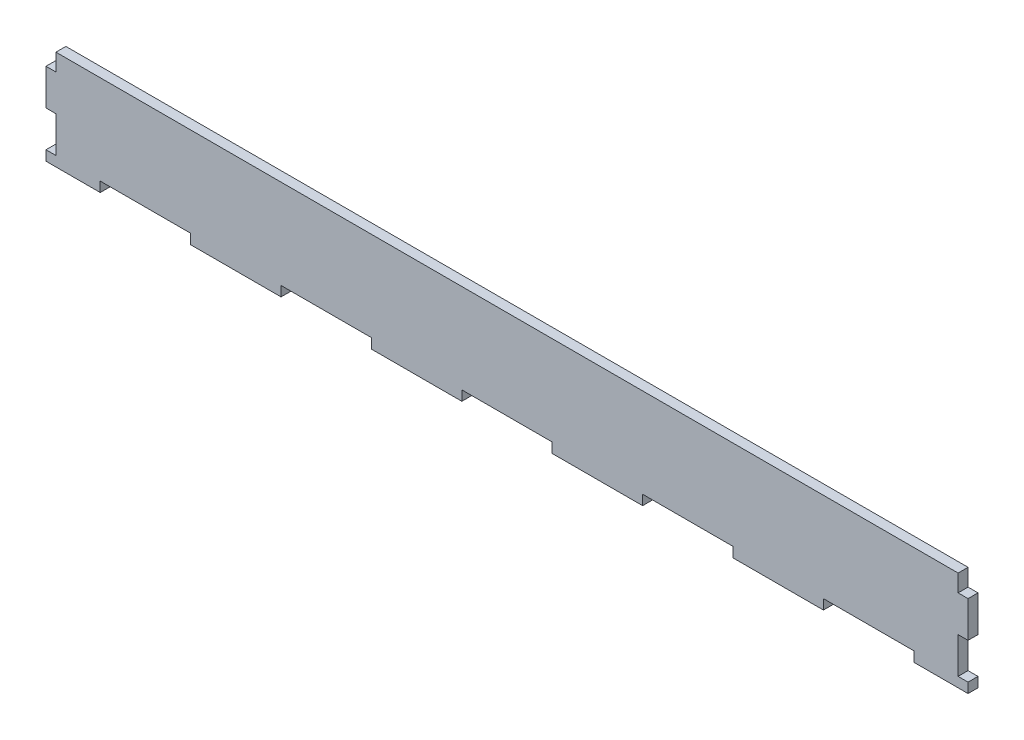
SolidWorks part; units mm, degrees
material "ﾁｰｸ材"
ref_plane "正面" through (0, 0, 0) normal (0, 0, 1) x (1, 0, 0)
ref_plane "平面" through (0, 0, 0) normal (0, 1, 0) x (1, 0, 0)
ref_plane "右側面" through (0, 0, 0) normal (1, 0, 0) x (0, 0, -1)
sketch "ｽｹｯﾁ1" plane through (0, 0, 0) normal (0, 0, 1) x (1, 0, 0)
  line L1 (255, 27.5) -> (-255, 27.5)
  line L2 (255, 27.5) -> (255, -27.5)
  line L3 (255, -27.5) -> (-255, -27.5)
  line L4 (-255, 27.5) -> (-255, -27.5)
  line L5 (255, 27.5) -> (-255, -27.5) construction
  line L6 (255, -27.5) -> (-255, 27.5) construction
  point P0 (0, 0)
  dimension "D1" = 55
  dimension "D2" = 510
extrude "ﾎﾞｽ - 押し出し1" add sketch "ｽｹｯﾁ1" along normal blind 5.5
sketch "ｽｹｯﾁ2" plane through (0, 0, 5.5) normal (0, 0, 1) x (1, 0, 0)
  line L0 (-255, -27.5) -> (255, -27.5) construction
  line L1 (-25, -27.5) -> (25, -27.5)
  line L2 (-25, -27.5) -> (-25, -22)
  line L3 (-25, -22) -> (25, -22)
  line L4 (25, -27.5) -> (25, -22)
  line L5 (-125, -27.5) -> (-75, -27.5)
  line L6 (75, -27.5) -> (125, -27.5)
  line L7 (75, -27.5) -> (75, -22)
  line L8 (75, -22) -> (125, -22)
  line L9 (125, -27.5) -> (125, -22)
  line L10 (-125, -27.5) -> (-125, -22)
  line L11 (-125, -22) -> (-75, -22)
  line L12 (-75, -27.5) -> (-75, -22)
  line L13 (175, -27.5) -> (225, -27.5)
  line L14 (175, -27.5) -> (175, -22)
  line L15 (175, -22) -> (225, -22)
  line L16 (225, -27.5) -> (225, -22)
  line L17 (-225, -27.5) -> (-175, -27.5)
  line L18 (-225, -27.5) -> (-225, -22)
  line L19 (-225, -22) -> (-175, -22)
  line L20 (-175, -27.5) -> (-175, -22)
  point P6 (0, -27.5)
  dimension "D1" = 5.5
  dimension "D2" = 50
  dimension "D3" = 5.5
  dimension "D4" = 50
  dimension "D5" = 50
  dimension "D6" = 50
  dimension "D7" = 5.5
  dimension "D8" = 50
  dimension "D9" = 5.5
  dimension "D10" = 50
  dimension "D11" = 50
  dimension "D12" = 50
  dimension "D13" = 50
extrude "ｶｯﾄ - 押し出し1" cut sketch "ｽｹｯﾁ2" against normal through all
sketch "ｽｹｯﾁ3" plane through (0, 0, 5.5) normal (0, 0, 1) x (1, 0, 0)
  line L0 (255, -27.5) -> (255, 27.5) construction
  line L1 (255, -22) -> (249.5, -22)
  line L2 (255, -22) -> (255, -2)
  line L3 (255, -2) -> (249.5, -2)
  line L4 (249.5, -22) -> (249.5, -2)
  line L5 (225, -27.5) -> (255, -27.5) construction
  line L6 (255, 18) -> (255, 38)
  line L7 (255, 18) -> (249.5, 18)
  line L8 (249.5, 18) -> (249.5, 38)
  line L9 (255, 38) -> (249.5, 38)
  line L10 (0, 0) -> (0, 15.2568) construction
  line L11 (-255, 18) -> (-249.5, 18)
  line L12 (-249.5, 18) -> (-249.5, 38)
  line L13 (-255, 38) -> (-249.5, 38)
  line L14 (-255, 18) -> (-255, 38)
  line L15 (-255, -2) -> (-249.5, -2)
  line L16 (-249.5, -22) -> (-249.5, -2)
  line L17 (-255, -22) -> (-249.5, -22)
  line L18 (-255, -22) -> (-255, -2)
  dimension "D1" = 5.5
  dimension "D2" = 20
  dimension "D3" = 5.5
  dimension "D4" = 2
extrude "ｶｯﾄ - 押し出し2" cut sketch "ｽｹｯﾁ3" against normal through all
